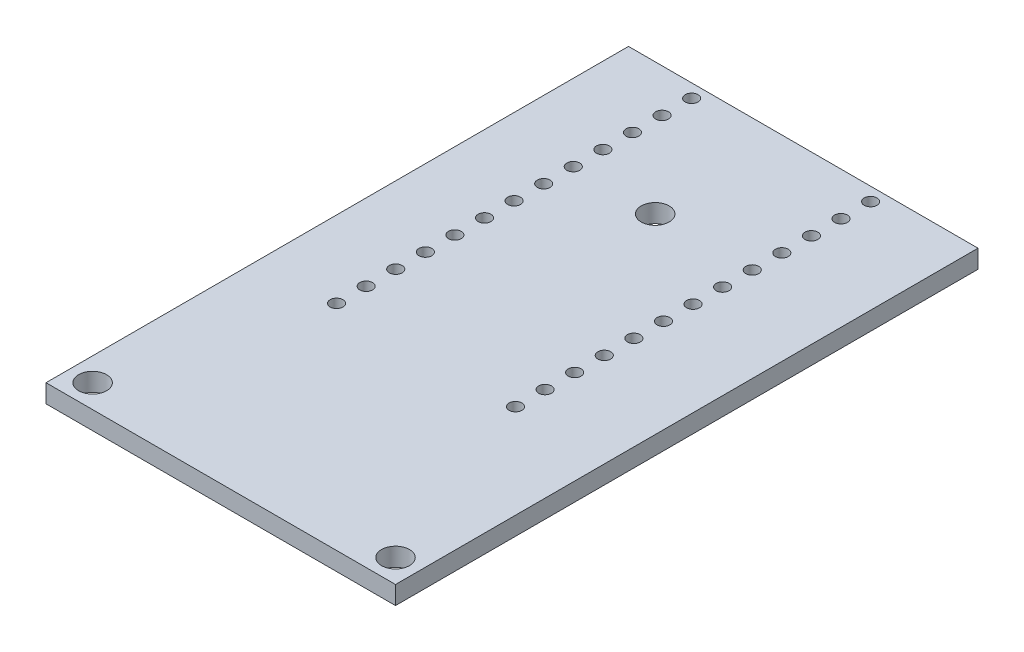
SolidWorks part; units mm, degrees
ref_plane "Front Plane" through (0, 0, 0) normal (0, 0, 1) x (1, 0, 0)
ref_plane "Top Plane" through (0, 0, 0) normal (0, 1, 0) x (1, 0, 0)
ref_plane "Right Plane" through (0, 0, 0) normal (1, 0, 0) x (0, 0, -1)
sketch "Sketch1" plane through (0, 0, 0) normal (0, 1, 0) x (1, 0, 0)
  line L1 (-15, -35) -> (15, -35)
  line L2 (-15, -35) -> (-15, 35)
  line L3 (-15, 35) -> (15, 35)
  line L4 (15, -35) -> (15, 35)
  line L5 (-15, -35) -> (15, 35) construction
  line L6 (-15, 35) -> (15, -35) construction
  point P0 (0, 0)
  dimension "D1" = 30
  dimension "D2" = 70
extrude "Boss-Extrude1" add sketch "Sketch1" along normal blind 1.57
hole_wizard "M2 Clearance Hole1" positions "Sketch3" profile "Sketch5" hole size "M2" standard "ISO" end condition up to next
sketch "Sketch3" plane through (0, 1.57, 0) normal (0, 1, 0) x (1, 0, 0)
  line L0 (15, -35) -> (15, 35) construction
  line L1 (15, 35) -> (-15, 35) construction
  line L3 (-13, -33) -> (13, -33)
  line L4 (-13, -33) -> (-13, 33)
  line L5 (-13, 33) -> (13, 33)
  line L6 (13, -33) -> (13, 33)
  line L7 (-13, -33) -> (13, 33) construction
  line L8 (-13, 33) -> (13, -33) construction
  point P0 (13, 33)
  point P2 (-13, 33)
  point P4 (-13, -33)
  point P6 (13, -33)
  dimension "D1" = 2
  dimension "D2" = 2
sketch "Sketch5" plane through (13, 1.57, -33) normal (1, 0, 0) x (0, 0, 1)
  line L0 (0, 0) -> (0, 1.57)
  line L1 (0, 1.57) -> (1.2, 1.57)
  line L2 (1.2, 1.57) -> (1.2, 0)
  line L5 (1.2, 0) -> (0, 0)
  line L11 (0, -6.35) -> (0, 107.95) construction
  dimension "Thru Hole Dia." = 2.4
  dimension "Thru Hole Depth" = 1.57
sketch "Sketch6" plane through (0, 1.57, 0) normal (0, 1, 0) x (1, 0, 0)
  line L0 (-8.08, 18.58) -> (-8.78, 19.28) construction
  line L1 (7.28, 18.58) -> (6.58, 19.28) construction
  circle A0 centre (6.93, 18.93) radius 0.55
  circle A1 centre (-8.43, 18.93) radius 0.55
  dimension "D1" = 1.1
extrude "Cut-Extrude1" cut sketch "Sketch6" against normal up to next
pattern_linear "LPattern1" count 15 spacing 2.54 along (0, 0, 1) of "Cut-Extrude1"
sketch "Sketch7" plane through (0, 0, 0) normal (0, -1, 0) x (1, 0, 0)
  line L0 (15, 35) -> (15, -35) construction
  line L1 (-15, -35) -> (15, -35)
  line L2 (-15, -35) -> (-15, -15)
  line L3 (-15, -15) -> (15, -15)
  line L4 (15, -35) -> (15, -15)
  line L5 (-15, 35) -> (15, 35) construction
  dimension "D1" = 50
extrude "Cut-Extrude2" cut sketch "Sketch7" against normal through all
hole_wizard "M2 Clearance Hole2" positions "Sketch8" profile "Sketch9" hole size "M2" standard "ISO" end condition up to next
sketch "Sketch8" plane through (0, 0, 0) normal (0, -1, 0) x (-1, 0, 0)
  line L0 (15, -35) -> (-15, -35) construction
  line L2 (15, 15) -> (15, -35) construction
  point P0 (1.4, 3.69)
  dimension "D1" = 38.69
  dimension "D2" = 13.6
sketch "Sketch9" plane through (-1.4, 0, -3.69) normal (1, 0, 0) x (0, 0, -1)
  line L0 (0, 0) -> (0, 1.57)
  line L1 (0, 1.57) -> (1.2, 1.57)
  line L2 (1.2, 1.57) -> (1.2, 0)
  line L5 (1.2, 0) -> (0, 0)
  line L11 (0, -6.35) -> (0, 107.95) construction
  dimension "Thru Hole Dia." = 2.4
  dimension "Thru Hole Depth" = 1.57
